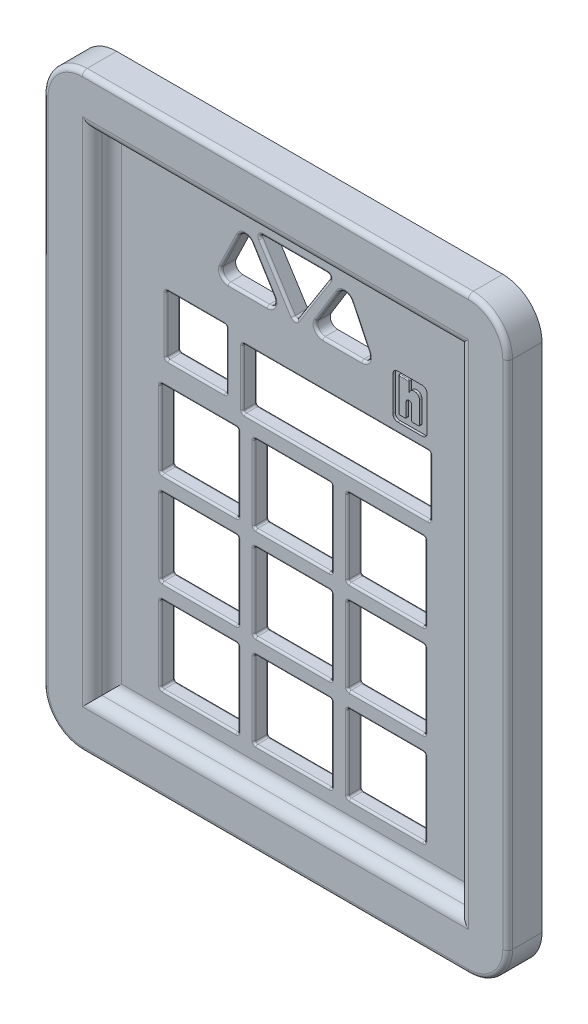
SolidWorks part; units mm, degrees
material "Custom Plastic"
ref_plane "Front Plane" through (0, 0, 0) normal (0, 0, 1) x (1, 0, 0)
ref_plane "Top Plane" through (0, 0, 0) normal (0, 1, 0) x (1, 0, 0)
ref_plane "Right Plane" through (0, 0, 0) normal (1, 0, 0) x (0, 0, -1)
sketch "Sketch2" plane through (0, 0, 0) normal (0, 0, 1) x (1, 0, 0)
  line L0 (-37.35, 50.1) -> (-37.35, -50.1)
  line L1 (-47.35, 60.1) -> (47.35, 60.1)
  line L2 (-47.35, 60.1) -> (-47.35, -60.1)
  line L3 (-47.35, -60.1) -> (47.35, -60.1)
  line L4 (47.35, 60.1) -> (47.35, -60.1)
  line L5 (-47.35, 60.1) -> (47.35, -60.1) construction
  line L6 (-47.35, -60.1) -> (47.35, 60.1) construction
  line L11 (-39.8215, 50.5442) -> (37.3875, -47.4549) construction
  line L12 (-38.75, -48.8846) -> (38.75, 48.8846) construction
  line L13 (-37.35, -50.1) -> (37.35, -50.1)
  line L14 (37.35, 50.1) -> (37.35, -50.1)
  line L15 (-37.35, 50.1) -> (37.35, 50.1)
  line L16 (64.2105, 0) -> (-67.7107, 0) construction
  line L21 (-37.25, 50) -> (37.25, 50) construction
  line L22 (-37.25, 50) -> (-37.25, -50) construction
  line L23 (-37.25, -50) -> (37.25, -50) construction
  line L24 (37.25, 50) -> (37.25, -50) construction
  line L25 (-37.25, 50) -> (37.25, -50) construction
  line L26 (-37.25, -50) -> (37.25, 50) construction
  line L27 (-7.51, 49.38) -> (9.99, 49.38) construction
  line L28 (-7.51, 49.38) -> (-7.51, 28.32) construction
  line L29 (-7.51, 28.32) -> (9.99, 28.32) construction
  line L30 (9.99, 49.38) -> (9.99, 28.32) construction
  line L31 (-7.51, 49.38) -> (9.99, 28.32) construction
  line L32 (-7.51, 28.32) -> (9.99, 49.38) construction
  line L33 (-26.3, 25.85) -> (-14, 25.85)
  line L34 (-26.3, 25.85) -> (-26.3, 13.75)
  line L35 (-26.3, 13.75) -> (-14, 13.75)
  line L36 (-14, 25.85) -> (-14, 13.75)
  line L37 (-26.3, 25.85) -> (-14, 13.75) construction
  line L38 (-26.3, 13.75) -> (-14, 25.85) construction
  line L39 (-10.69, 24.28) -> (27.51, 24.28)
  line L40 (-10.69, 24.28) -> (-10.69, 12.08)
  line L41 (-10.69, 12.08) -> (27.51, 12.08)
  line L42 (27.51, 24.28) -> (27.51, 12.08)
  line L43 (-10.69, 24.28) -> (27.51, 12.08) construction
  line L44 (-10.69, 12.08) -> (27.51, 24.28) construction
  line L45 (-27.41, 8.89) -> (-11.61, 8.89)
  line L46 (-27.41, 8.89) -> (-27.41, -6.91)
  line L47 (-27.41, -6.91) -> (-11.61, -6.91)
  line L48 (-11.61, 8.89) -> (-11.61, -6.91)
  line L49 (-27.41, 8.89) -> (-11.61, -6.91) construction
  line L50 (-27.41, -6.91) -> (-11.61, 8.89) construction
  line L51 (-8.36, 8.69) -> (7.44, 8.69)
  line L52 (-8.36, 8.69) -> (-8.36, -7.11)
  line L53 (-8.36, -7.11) -> (7.44, -7.11)
  line L54 (7.44, 8.69) -> (7.44, -7.11)
  line L55 (-8.36, 8.69) -> (7.44, -7.11) construction
  line L56 (-8.36, -7.11) -> (7.44, 8.69) construction
  line L57 (10.69, 8.69) -> (26.49, 8.69)
  line L58 (10.69, 8.69) -> (10.69, -7.11)
  line L59 (10.69, -7.11) -> (26.49, -7.11)
  line L60 (26.49, 8.69) -> (26.49, -7.11)
  line L61 (10.69, 8.69) -> (26.49, -7.11) construction
  line L62 (10.69, -7.11) -> (26.49, 8.69) construction
  line L63 (-27.41, -10.16) -> (-11.61, -10.16)
  line L64 (-27.41, -10.16) -> (-27.41, -25.96)
  line L65 (-27.41, -25.96) -> (-11.61, -25.96)
  line L66 (-11.61, -10.16) -> (-11.61, -25.96)
  line L67 (-27.41, -10.16) -> (-11.61, -25.96) construction
  line L68 (-27.41, -25.96) -> (-11.61, -10.16) construction
  line L69 (-8.36, -10.36) -> (7.44, -10.36)
  line L70 (-8.36, -10.36) -> (-8.36, -26.16)
  line L71 (-8.36, -26.16) -> (7.44, -26.16)
  line L72 (7.44, -10.36) -> (7.44, -26.16)
  line L73 (-8.36, -10.36) -> (7.44, -26.16) construction
  line L74 (-8.36, -26.16) -> (7.44, -10.36) construction
  line L75 (10.69, -10.36) -> (26.49, -10.36)
  line L76 (10.69, -10.36) -> (10.69, -26.16)
  line L77 (10.69, -26.16) -> (26.49, -26.16)
  line L78 (26.49, -10.36) -> (26.49, -26.16)
  line L79 (10.69, -10.36) -> (26.49, -26.16) construction
  line L80 (10.69, -26.16) -> (26.49, -10.36) construction
  line L81 (-27.41, -29.21) -> (-11.61, -29.21)
  line L82 (-27.41, -29.21) -> (-27.41, -45.01)
  line L83 (-27.41, -45.01) -> (-11.61, -45.01)
  line L84 (-11.61, -29.21) -> (-11.61, -45.01)
  line L85 (-27.41, -29.21) -> (-11.61, -45.01) construction
  line L86 (-27.41, -45.01) -> (-11.61, -29.21) construction
  line L87 (-8.36, -29.41) -> (7.44, -29.41)
  line L88 (-8.36, -29.41) -> (-8.36, -45.21)
  line L89 (-8.36, -45.21) -> (7.44, -45.21)
  line L90 (7.44, -29.41) -> (7.44, -45.21)
  line L91 (-8.36, -29.41) -> (7.44, -45.21) construction
  line L92 (-8.36, -45.21) -> (7.44, -29.41) construction
  line L93 (10.69, -29.41) -> (26.49, -29.41)
  line L94 (10.69, -29.41) -> (10.69, -45.21)
  line L95 (10.69, -45.21) -> (26.49, -45.21)
  line L96 (26.49, -29.41) -> (26.49, -45.21)
  line L97 (10.69, -29.41) -> (26.49, -45.21) construction
  line L98 (10.69, -45.21) -> (26.49, -29.41) construction
  line L99 (0, -66.124) -> (0, 69.8281) construction
  circle A0 centre (-42.35, 55.1) radius 1.45
  circle A4 centre (42.35, 55.1) radius 1.45
  circle A5 centre (42.35, -55.1) radius 1.45
  circle A6 centre (-42.35, -55.1) radius 1.45
  point P0 (0, 0)
  point P6 (0, 0)
  point P15 (0, 0)
  point P16 (1.24, 38.85)
  point P25 (-20.15, 19.8)
  point P30 (8.41, 18.18)
  point P35 (-19.51, 0.99)
  point P40 (-0.46, 0.79)
  point P45 (18.59, 0.79)
  point P50 (-19.51, -18.06)
  point P55 (-0.46, -18.26)
  point P60 (18.59, -18.26)
  point P65 (-19.51, -37.11)
  point P70 (-0.46, -37.31)
  point P75 (18.59, -37.31)
  dimension "D54" = 2.9
  dimension "D55" = 5
  dimension "D56" = 5
  dimension "D1" = 120.2
  dimension "D2" = 94.7
  dimension "D3" = 10
  dimension "D4" = 74.5
  dimension "D5" = 100
  dimension "D6" = 21.06
  dimension "D7" = 17.5
  dimension "D8" = 29.74
  dimension "D9" = 12.3
  dimension "D10" = 12.1
  dimension "D11" = 10.95
  dimension "D12" = 24.15
  dimension "D13" = 38.2
  dimension "D14" = 12.2
  dimension "D15" = 9.74
  dimension "D16" = 25.72
  dimension "D17" = 4.04
  dimension "D18" = 15.8
  dimension "D19" = 15.8
  dimension "D20" = 4.86
  dimension "D21" = 9.84
  dimension "D22" = 15.8
  dimension "D23" = 15.8
  dimension "D24" = 3.25
  dimension "D25" = 3.39
  dimension "D26" = 15.8
  dimension "D27" = 15.8
  dimension "D28" = 3.25
  dimension "D29" = 3.39
  dimension "D30" = 15.8
  dimension "D31" = 15.8
  dimension "D32" = 9.84
  dimension "D33" = 3.25
  dimension "D34" = 15.8
  dimension "D35" = 15.8
  dimension "D36" = 3.25
  dimension "D37" = 3.25
  dimension "D38" = 15.8
  dimension "D39" = 15.8
  dimension "D40" = 3.25
  dimension "D41" = 15.8
  dimension "D42" = 9.84
  dimension "D43" = 3.25
  dimension "D44" = 3.25
  dimension "D45" = 15.8
  dimension "D46" = 15.8
  dimension "D47" = 15.8
  dimension "D48" = 3.25
  dimension "D49" = 3.25
  dimension "D50" = 15.8
  dimension "D51" = 15.8
  dimension "D52" = 3.25
  dimension "D53" = 3.25
extrude "Boss-Extrude2" add sketch "Sketch2" along normal blind 3 contours L15 L0 L13 L14 L33 L36 L35 L34 L39 L42 L41 L40 L45 L48 L47 L46 L51 L54 L53 L52 L57 L60 L59 L58 L63 L66 L65 L64 L69 L72 L71 L70 L75 L78 L77 L76 L81 L84 L83 L82 L87 | L4 L1 L2 L3 L0 L15 L14 L13 region at (0, 48.8502, 0) region at (0, 58.5698, 0)
fillet "Fillet1" radius 0.4 132 edges at (10.69, -18.26, 3) (10.69, -18.26, 0) (-20.15, 25.85, 3) (8.41, 24.28, 3) (18.59, 8.69, 3) (-0.46, 8.69, 3) (-19.51, 8.89, 3) (-19.51, -10.16, 3) (8.41, 24.28, 0) (-20.15, 25.85, 0) (18.59, 8.69, 0) (-0.46, 8.69, 0) (-19.51, 8.89, 0) (7.44, -18.26, 0) (-11.61, -18.06, 0) (18.59, -29.41, 0) (-0.46, -29.41, 0) (-19.51, -29.21, 0) (-19.51, -45.01, 3) (7.44, -37.31, 3) (-0.46, -26.16, 3) (18.59, -10.36, 3) (18.59, -10.36, 0) (18.59, -26.16, 3) (18.59, -26.16, 0) (-26.3, 19.8, 3) (-14, 19.8, 3) (-10.69, 18.18, 3) (27.51, 18.18, 3) (10.69, 0.79, 3) (26.49, 0.79, 3) (-8.36, 0.79, 3) (7.44, 0.79, 3) (-27.41, 0.99, 3) (-11.61, 0.99, 3) (-27.41, -18.06, 3) (-11.61, -18.06, 3) (-10.69, 18.18, 0) (27.51, 18.18, 0) (-26.3, 19.8, 0) (-14, 19.8, 0) (10.69, 0.79, 0) (26.49, 0.79, 0) (-8.36, 0.79, 0) (7.44, 0.79, 0) (-27.41, 0.99, 0) (-11.61, 0.99, 0) (-0.46, -10.36, 0) (-0.46, -26.16, 0) (-19.51, -10.16, 0) (-19.51, -25.96, 0) (10.69, -37.31, 0) (26.49, -37.31, 0) (-8.36, -37.31, 0) (7.44, -37.31, 0) (-27.41, -37.11, 0) (-11.61, -37.11, 0) (-27.41, -37.11, 3) (-11.61, -37.11, 3) (-0.46, -29.41, 3) (-0.46, -45.21, 3) (26.49, -37.31, 3) (10.69, -37.31, 3) (-8.36, -18.26, 3) (7.44, -18.26, 3) (26.49, -10.36, 1.5) (26.49, -18.26, 3) (26.49, -26.16, 1.5) (26.49, -18.26, 0) (-20.15, 13.75, 3) (8.41, 12.08, 3) (18.59, -7.11, 3) (-0.46, -7.11, 3) (-19.51, -6.91, 3) (-19.51, -25.96, 3) (8.41, 12.08, 0) (-20.15, 13.75, 0) (18.59, -7.11, 0) (-0.46, -7.11, 0) (-19.51, -6.91, 0) (-8.36, -18.26, 0) (-27.41, -18.06, 0) (18.59, -45.21, 0) (-0.46, -45.21, 0) (-19.51, -45.01, 0) (-19.51, -29.21, 3) (-27.41, -29.21, 1.5) (-27.41, -45.01, 1.5) (-11.61, -45.01, 1.5) (-11.61, -29.21, 1.5) (-8.36, -37.31, 3) (-8.36, -29.41, 1.5) (-8.36, -45.21, 1.5) (7.44, -45.21, 1.5) (7.44, -29.41, 1.5) (10.69, -26.16, 1.5) (10.69, -45.21, 1.5) (26.49, -45.21, 1.5) (18.59, -45.21, 3) (26.49, -29.41, 1.5) (10.69, -29.41, 1.5) (18.59, -29.41, 3) (-0.46, -10.36, 3) (10.69, -10.36, 1.5) (-8.36, -26.16, 1.5) (7.44, -26.16, 1.5) (7.44, -10.36, 1.5) (-8.36, -10.36, 1.5) (-27.41, -25.96, 1.5) (-11.61, -25.96, 1.5) (-11.61, -10.16, 1.5) (-27.41, -10.16, 1.5) (26.49, -7.11, 1.5) (26.49, 8.69, 1.5) (10.69, -7.11, 1.5) (10.69, 8.69, 1.5) (7.44, 8.69, 1.5) (7.44, -7.11, 1.5) (-8.36, -7.11, 1.5) (-8.36, 8.69, 1.5) (-10.69, 24.28, 1.5) (27.51, 24.28, 1.5) (27.51, 12.08, 1.5) (-10.69, 12.08, 1.5) (-27.41, -6.91, 1.5) (-11.61, -6.91, 1.5) (-27.41, 8.89, 1.5) (-11.61, 8.89, 1.5) (-26.3, 13.75, 1.5) (-14, 13.75, 1.5) (-14, 25.85, 1.5) (-26.3, 25.85, 1.5)
sketch "Sketch4" plane through (0, 0, 3) normal (0, 0, 1) x (1, 0, 0)
  line L0 (-47.35, 60.1) -> (-47.35, -60.1)
  line L1 (-37.35, 50.1) -> (37.35, 50.1)
  line L2 (-37.35, 50.1) -> (-37.35, -50.1)
  line L3 (-37.35, -50.1) -> (37.35, -50.1)
  line L4 (37.35, 50.1) -> (37.35, -50.1)
  line L5 (-37.35, 50.1) -> (37.35, -50.1) construction
  line L6 (-37.35, -50.1) -> (37.35, 50.1) construction
  line L7 (-47.35, -60.1) -> (47.35, -60.1)
  line L8 (47.35, -60.1) -> (47.35, 60.1)
  line L9 (47.35, 60.1) -> (-47.35, 60.1)
  point P0 (0, 0)
  dimension "D1" = 100.2
  dimension "D2" = 74.7
extrude "Boss-Extrude3" add sketch "Sketch4" along normal blind 4
fillet "Fillet2" radius 2 4 edges at (0, -50.1, 7) (37.35, 0, 7) (-37.35, 0, 7) (0, 50.1, 7)
fillet "Fillet3" radius 2 4 edges at (0, -50.1, 3) (37.35, 0, 3) (-37.35, 0, 3) (0, 50.1, 3)
fillet "Fillet4" radius 8 4 edges at (-47.35, -60.1, 3.5) (47.35, -60.1, 3.5) (47.35, 60.1, 3.5) (-47.35, 60.1, 3.5)
fillet "Fillet5" radius 1 8 edges at (45.0069, 57.7569, 7) (47.35, 0, 7) (45.0069, -57.7569, 7) (0, -60.1, 7) (-45.0069, -57.7569, 7) (-47.35, 0, 7) (-45.0069, 57.7569, 7) (0, 60.1, 7)
sketch "Sketch5" plane through (0, 0, 3) normal (0, 0, 1) x (1, 0, 0)
  line L0 (0, 69.5452) -> (0, -70.7503) construction
  line L1 (21.0643, 27.7466) -> (22.6643, 27.7466)
  line L2 (19.937, 35.2971) -> (26.937, 35.2971)
  line L3 (19.937, 35.2971) -> (19.937, 26.2971)
  line L4 (19.937, 26.2971) -> (26.937, 26.2971)
  line L5 (26.937, 35.2971) -> (26.937, 26.2971)
  line L6 (19.937, 35.2971) -> (26.937, 26.2971) construction
  line L7 (19.937, 26.2971) -> (26.937, 35.2971) construction
  line L8 (22.6643, 27.7466) -> (22.6643, 30.7355)
  line L9 (23.7954, 30.7355) -> (23.7954, 27.7466)
  line L14 (21.0643, 34.8079) -> (21.0643, 27.7466)
  line L15 (23.7954, 27.7466) -> (25.3954, 27.7466)
  line L16 (21.0643, 34.8079) -> (23.2299, 34.8079)
  line L17 (23.2299, 34.8079) -> (23.2299, 32.3564)
  line L18 (25.3954, 32.3564) -> (25.3954, 27.7466)
  arc A0 (22.6643, 30.7355) -> (23.7954, 30.7355) centre (23.2299, 30.7355) cw
  arc A2 (23.2299, 32.3564) -> (25.3954, 32.3564) centre (24.3127, 32.3564) cw
  point P3 (23.437, 30.7971)
  dimension "D1" = 9
  dimension "D2" = 7
  dimension "D3" = 1.6
  dimension "D4" = 1.6
extrude "Cut-Extrude1" cut sketch "Sketch5" against normal blind 0.5
fillet "Fillet6" radius 1 4 edges at (19.937, 26.2971, 2.75) (26.937, 26.2971, 2.75) (26.937, 35.2971, 2.75) (19.937, 35.2971, 2.75)
fillet "Fillet8" radius 0.2 8 edges at (22.1471, 34.8079, 3) (21.0643, 31.2772, 3) (21.0643, 34.8079, 2.75) (23.2299, 34.8079, 2.75) (25.3954, 27.7466, 2.75) (23.7954, 27.7466, 2.75) (21.0643, 27.7466, 2.75) (22.6643, 27.7466, 2.75)
sketch "Sketch6" plane through (0, 0, 3) normal (0, 0, 1) x (1, 0, 0)
  line L0 (0, 80.5191) -> (0, -78.2638) construction
  line L1 (0, 33.5284) -> (7.5, 45.35)
  line L2 (7.5, 45.35) -> (-7.5, 45.35)
  line L3 (-7.5, 45.35) -> (0, 33.5284)
  line L4 (35.35, 48.1) -> (-35.35, 48.1) construction
  line L6 (-16, 33.5284) -> (-3, 33.5284)
  line L18 (-3, 33.5284) -> (-10.2799, 45.35)
  line L19 (-10.2799, 45.35) -> (-16, 33.5284)
  line L20 (3, 33.5284) -> (10.2799, 45.35)
  line L21 (16, 33.5284) -> (3, 33.5284)
  line L22 (10.2799, 45.35) -> (16, 33.5284)
  dimension "D1" = 14
  dimension "D2" = 14
  dimension "D3" = 15
  dimension "D4" = 2.75
  dimension "D5" = 13
  dimension "D6" = 3
extrude "Cut-Extrude2" cut sketch "Sketch6" against normal blind 10
fillet "Fillet15" radius 1.5 6 edges at (16, 33.5284, 1.5) (3, 33.5284, 1.5) (10.2799, 45.35, 1.5) (-3, 33.5284, 1.5) (-16, 33.5284, 1.5) (-10.2799, 45.35, 1.5)
fillet "Fillet16" radius 0.5 18 edges at (3.75, 39.4392, 3) (-3.75, 39.4392, 3) (10.1978, 43.7308, 3) (13.2151, 39.2839, 3) (14.8787, 34.2315, 3) (9.6466, 33.5284, 3) (4.3758, 34.2969, 3) (-4.3758, 34.2969, 3) (-9.6466, 33.5284, 3) (-14.8787, 34.2315, 3) (-13.2151, 39.2839, 3) (-10.1978, 43.7308, 3) (6.6264, 39.4171, 3) (-6.6264, 39.4171, 3) (0, 45.35, 3) (0, 33.5284, 1.5) (7.5, 45.35, 1.5) (-7.5, 45.35, 1.5)
